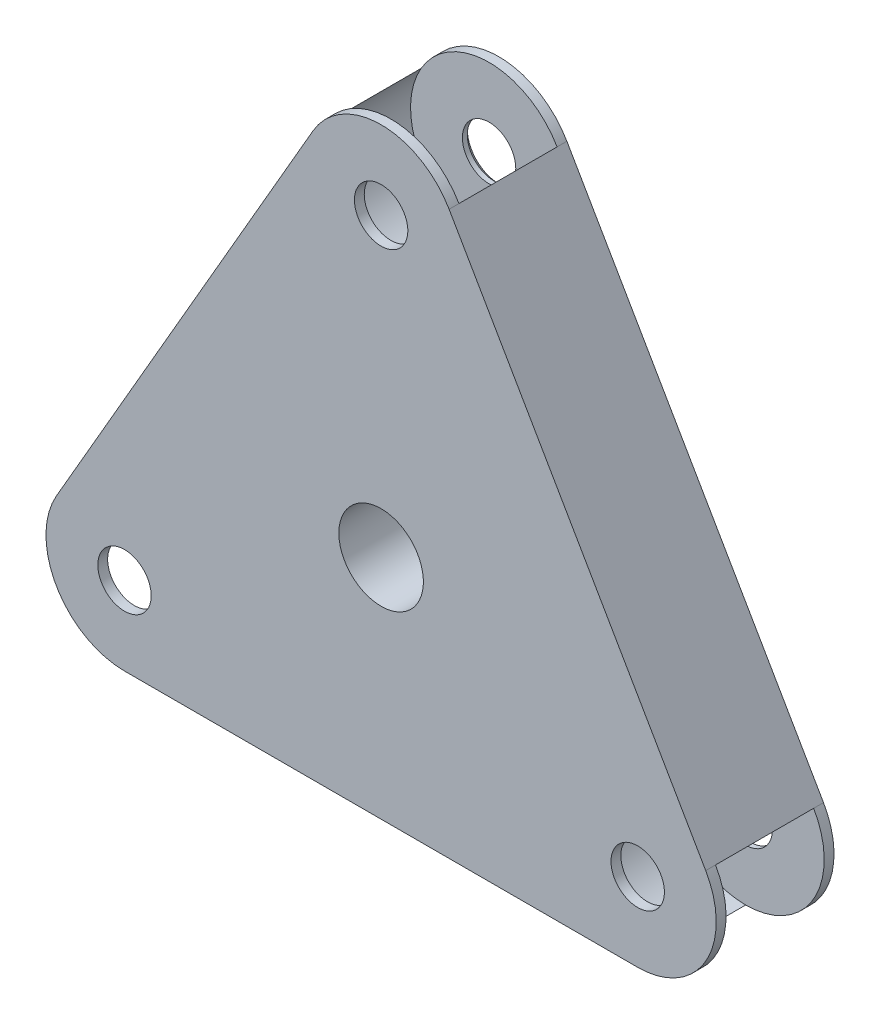
SolidWorks part; units mm, degrees
ref_plane "Plan de face" through (0, 0, 0) normal (0, 0, 1) x (1, 0, 0)
ref_plane "Plan de dessus" through (0, 0, 0) normal (0, 1, 0) x (1, 0, 0)
ref_plane "Plan de droite" through (0, 0, 0) normal (1, 0, 0) x (0, 0, -1)
sketch "Esquisse1" plane through (0, 0, 0) normal (0, 0, 1) x (1, 0, 0)
  line L1 (-8.6603, 42.735) -> (-41.3397, -13.8675)
  line L2 (-32.6795, -28.8675) -> (32.6795, -28.8675)
  line L3 (41.3397, -13.8675) -> (8.6603, 42.735)
  circle A0 centre (0, 0) radius 28.8675 construction
  arc A1 (32.6795, -28.8675) -> (41.3397, -13.8675) centre (32.6795, -18.8675) ccw
  arc A2 (-41.3397, -13.8675) -> (-32.6795, -28.8675) centre (-32.6795, -18.8675) ccw
  arc A3 (-8.6603, 42.735) -> (8.6603, 42.735) centre (0, 37.735) cw
  point P8 (50, -28.8675)
  point P13 (0, 57.735)
  dimension "D2" = 10
  dimension "D1" = 100
extrude "Boss.-Extru.1" add sketch "Esquisse1" along normal blind 15
sketch "Esquisse2" plane through (0, 0, 0) normal (0, 0, 1) x (1, 0, 0)
  circle A0 centre (0, 37.735) radius 10
  arc A1 (8.6603, 42.735) -> (-8.6603, 42.735) centre (0, 37.735) ccw construction
extrude "Enlèv. mat.-Extru.1" cut sketch "Esquisse2" against normal mid plane 12.5 from offset 7.5
sketch "Esquisse3" plane through (0, 0, 0) normal (0, 1, 0) x (1, 0, 0)
  line L0 (0, 0.5506) -> (0, 12.8411) construction
pattern_circular "Répétition circulaire1" count 3 over 360 about axis through (0, 0, -0.5506) along (0, 0, -1) of "Enlèv. mat.-Extru.1"
sketch "Esquisse6" plane through (0, 0, 0) normal (0, 0, -1) x (-1, 0, 0)
  arc A0 (8.6603, 42.735) -> (-8.6603, 42.735) centre (0, 37.735) ccw construction
  arc A1 (-41.3397, -13.8675) -> (-32.6795, -28.8675) centre (-32.6795, -18.8675) ccw construction
  arc A2 (32.6795, -28.8675) -> (41.3397, -13.8675) centre (32.6795, -18.8675) ccw construction
  point P0 (0, 37.735)
  point P2 (32.6795, -18.8675)
  point P5 (-32.6795, -18.8675)
  point P12 (0, 0)
hole_wizard "Trou taraudé M81" positions "Esquisse6" profile "Esquisse5" tap size "M8" standard "ISO" end condition through all
sketch "Esquisse5" plane through (0, 37.735, 0) normal (1, 0, 0) x (0, 1, 0)
  line L0 (0, 0) -> (0, 15)
  line L1 (0, 15) -> (3.4, 15)
  line L2 (3.4, 15) -> (3.4, 0.625)
  line L3 (3.4, 0.625) -> (4.025, 0)
  line L5 (4.025, 0) -> (0, 0)
  line L6 (-3.4, 0.625) -> (-4.025, 0) construction
  line L11 (0, -6.35) -> (0, 107.95) construction
  dimension "Diamètre du trou pour taraudage jusqu'au prochain" = 6.8
  dimension "Profondeur du trou pour taraudage jusqu'au prochain" = 15
  dimension "Diamètre du fraisage entrant" = 8.05
  dimension "Angle du fraisage entrant" = 90
cosmetic thread "Filetage de perçage1" parameters "D2"=8
cosmetic thread "Filetage de perçage2" parameters "D2"=8
cosmetic thread "Filetage de perçage3" parameters "D2"=8
sketch "Esquisse7" plane through (0, 0, 0) normal (0, 0, -1) x (-1, 0, 0)
  circle A0 centre (0, 0) radius 5.3832
  circle A1 centre (0, 0) radius 7.4602
extrude "Boss.-Extru.2" add sketch "Esquisse7" along normal blind 12.5
extrude "Enlèv. mat.-Extru.2" cut sketch "Esquisse7<3>" against normal through all contours A0
sketch "Esquisse7<3>" plane through (0, 0, 0) normal (0, 0, -1) x (-1, 0, 0) same geometry as "Esquisse7"
